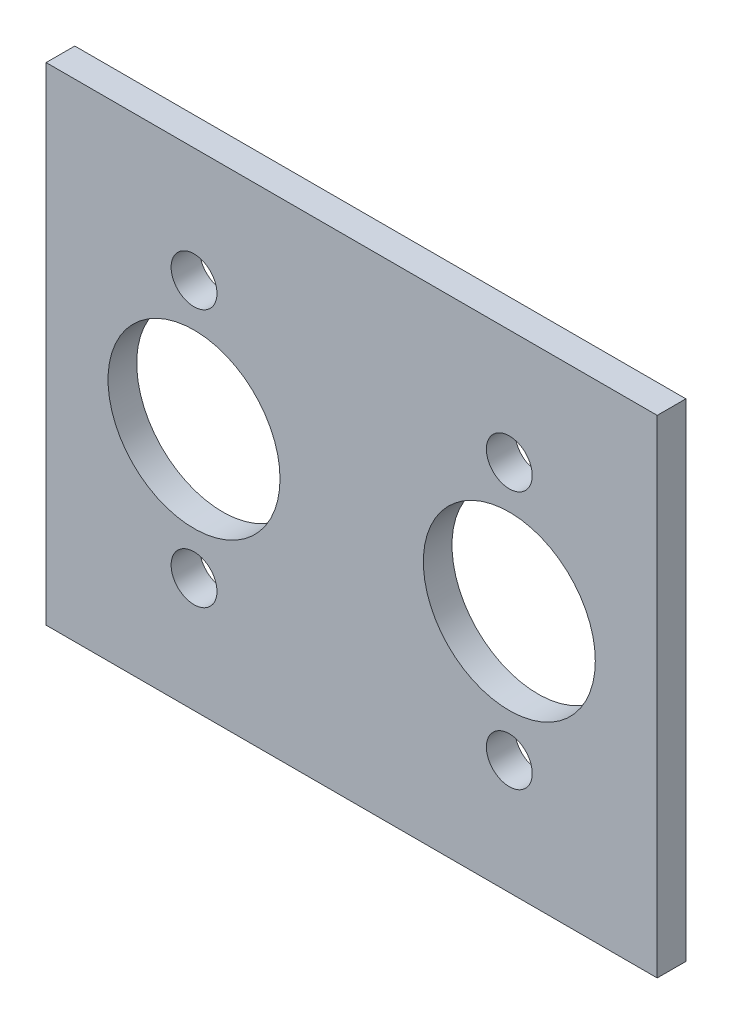
SolidWorks part; units mm, degrees
ref_plane "Płaszczyzna przednia" through (0, 0, 0) normal (0, 0, 1) x (1, 0, 0)
ref_plane "Płaszczyzna górna" through (0, 0, 0) normal (0, 1, 0) x (1, 0, 0)
ref_plane "Płaszczyzna prawa" through (0, 0, 0) normal (1, 0, 0) x (0, 0, -1)
sketch "Szkic1" plane through (0, 0, 0) normal (0, 0, 1) x (1, 0, 0)
  line L1 (-53.3, -42.5) -> (53.3, -42.5)
  line L2 (-53.3, -42.5) -> (-53.3, 42.5)
  line L3 (-53.3, 42.5) -> (53.3, 42.5)
  line L4 (53.3, -42.5) -> (53.3, 42.5)
  line L5 (-53.3, -42.5) -> (53.3, 42.5) construction
  line L6 (-53.3, 42.5) -> (53.3, -42.5) construction
  point P0 (0, 0)
  dimension "D1" = 106.6
  dimension "D2" = 85
base flange "Odgięcie bazowe1" sketch "Szkic1" thickness 5 reverse thickness direction no parameters "D1"=0.7366
sketch "Szkic6" plane through (0, 0, 0) normal (0, 0, 1) x (1, 0, 0)
  line L0 (0, 0) -> (0, 62.7878) construction
  line L1 (0, 0) -> (66.1839, 0) construction
  circle A0 centre (-27.5, 0) radius 15
  circle A1 centre (27.5, 0) radius 15
  circle A2 centre (-27.5, 22.5) radius 4
  circle A3 centre (27.5, 22.5) radius 4
  circle A4 centre (27.5, -22.5) radius 4
  circle A5 centre (-27.5, -22.5) radius 4
  dimension "D1" = 30
  dimension "D3" = 8
  dimension "D2" = 55
  dimension "D4" = 45
extrude "Wytnij-wyciągnięcie1" cut sketch "Szkic6" against normal through all normal cut yes
sketch "Linie zgięcia1" [suppressed] plane through (0, 0, 0) normal (0, 1, 0) x (1, 0, 0)
sketch "Ramka-graniczna1" [suppressed] plane through (0, 0, 0) normal (0, 1, 0) x (1, 0, 0)
sheet metal parameters "Arkusz blachy1" thickness 5 parameters "D1"=0.7366
flat pattern "Rozłożony model1" [suppressed]
sketch "Linie zgięcia2" plane through (0, 0, 0) normal (0, 1, 0) x (1, 0, 0)
sketch3d "Ramka-graniczna2" [suppressed]
  line L0 (53.3, -42.5, 0) -> (-53.3, -42.5, 0) construction
  line L1 (53.3, 42.5, 0) -> (-53.3, 42.5, 0) construction
  line L2 (53.3, -42.5, 0) -> (53.3, 42.5, 0) construction
  line L3 (-53.3, -42.5, 0) -> (-53.3, 42.5, 0) construction
sheet metal parameters "Arkusz blachy2" thickness 5 parameters "D1"=0.7366
flat pattern "Rozłożony model1"
sketch "Linie zgięcia2" plane through (0, 0, 0) normal (0, 1, 0) x (1, 0, 0)
sketch3d "Ramka-graniczna2" [suppressed]
  line L0 (-53.3, -42.5, 0) -> (53.3, -42.5, 0) construction
  line L1 (-53.3, 42.5, 0) -> (53.3, 42.5, 0) construction
  line L2 (-53.3, -42.5, 0) -> (-53.3, 42.5, 0) construction
  line L3 (53.3, -42.5, 0) -> (53.3, 42.5, 0) construction
